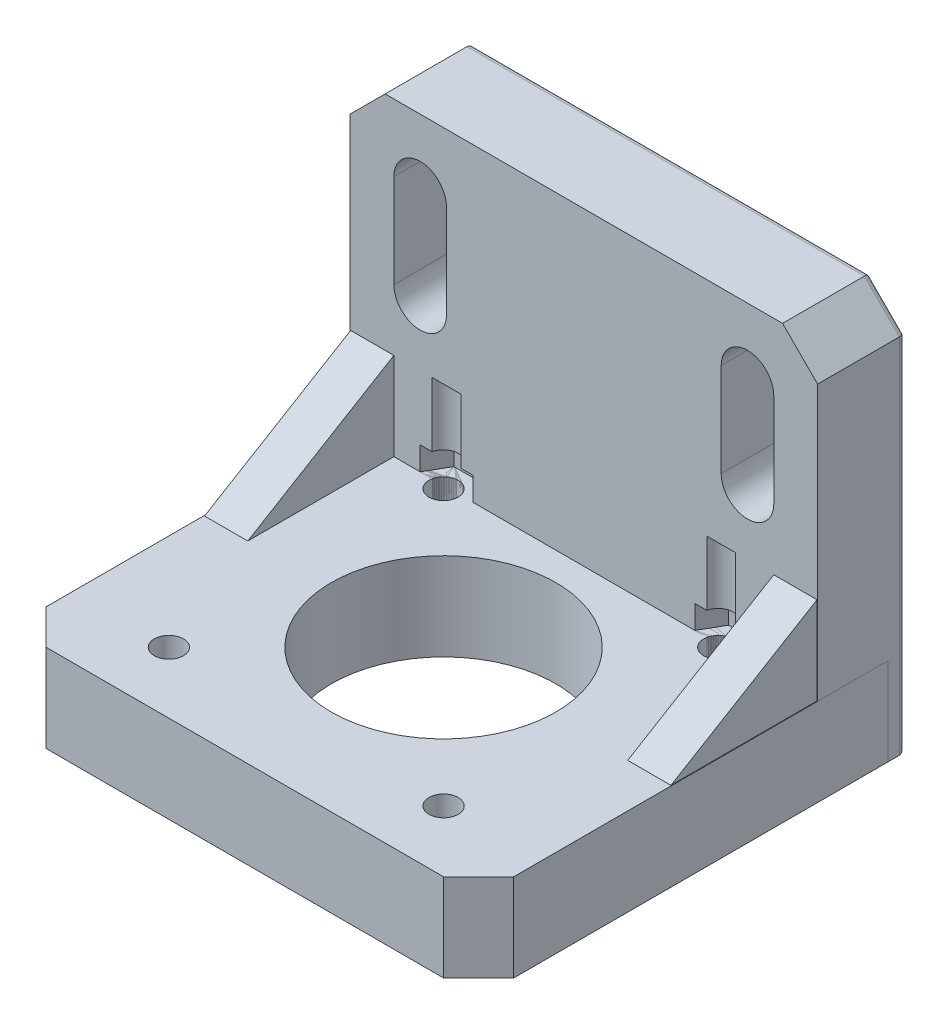
SolidWorks part; units mm, degrees
ref_plane "Front Plane" through (0, 0, 0) normal (0, 0, 1) x (1, 0, 0)
ref_plane "Top Plane" through (0, 0, 0) normal (0, 1, 0) x (1, 0, 0)
ref_plane "Right Plane" through (0, 0, 0) normal (1, 0, 0) x (0, 0, -1)
sketch "Sketch1" plane through (0, 0, 0) normal (0, 1, 0) x (1, 0, 0)
  line L1 (-32.5, -5) -> (47.5, -5)
  line L2 (-32.5, -5) -> (-32.5, 65)
  line L3 (-32.5, 65) -> (47.5, 65)
  line L4 (47.5, -5) -> (47.5, 65)
  dimension "D1" = 70
  dimension "D2" = 80
  dimension "D3" = 32.5
extrude "Boss-Extrude1" add sketch "Sketch1" along normal blind 15
sketch "Sketch2" plane through (0, 0, 0) normal (0, -1, 0) x (1, 0, 0)
  line L0 (47.5, 5) -> (47.5, -65) construction
  line L1 (-32.5, -65) -> (47.5, -65)
  line L2 (-32.5, -65) -> (-32.5, -68)
  line L3 (-32.5, -68) -> (47.5, -68)
  line L4 (47.5, -65) -> (47.5, -68)
  line L5 (-32.5, -53) -> (47.5, -53)
  line L6 (-32.5, -65) -> (-32.5, 5) construction
  line M2 (-32.5, 5) -> (-32.5, -65)
  line M3 (-32.5, -65) -> (47.5, -65)
  line M4 (47.5, -65) -> (47.5, 5)
  dimension "D1" = 3
  dimension "D2" = 12
extrude "Boss-Extrude2" add sketch "Sketch2" against normal blind 68 separate body contours L4 L2 L3 M3 | L5 M2 M3 M4 region at (7.5, 0, -59) region at (7.5, 0, -66.5)
sketch "Sketch4" plane through (0, 15, 0) normal (0, 1, 0) x (1, 0, 0)
  line L0 (-32.5, 65) -> (-32.5, -5) construction
  line L2 (-32.5, 68) -> (47.5, 68) construction
  circle A0 centre (7.5, 29) radius 19.2
  point P7 (7.5, 9.8)
  dimension "D1" = 38.4
  dimension "D2" = 39
  dimension "D3" = 40
  dimension "D4" = 39
extrude "Cut-Extrude1" cut sketch "Sketch4" against normal through all
sketch "Sketch5" plane through (0, 15, 0) normal (0, 1, 0) x (1, 0, 0)
  line L0 (33.396, 48.35) -> (28.604, 48.35)
  line L1 (-16, 52.5) -> (31, 52.5) construction
  line L2 (-16, 52.5) -> (-16, 5.5) construction
  line L3 (-16, 5.5) -> (31, 5.5) construction
  line L4 (31, 52.5) -> (31, 5.5) construction
  line L5 (-16, 52.5) -> (31, 5.5) construction
  line L6 (-16, 5.5) -> (31, 52.5) construction
  line L7 (28.604, 48.35) -> (26.208, 52.5)
  line L8 (26.208, 52.5) -> (28.604, 56.65)
  line L9 (28.604, 56.65) -> (33.396, 56.65)
  line L10 (33.396, 56.65) -> (35.792, 52.5)
  line L11 (35.792, 52.5) -> (33.396, 48.35)
  line L12 (-13.602, 56.65) -> (-11.206, 52.5)
  line L13 (-18.394, 48.35) -> (-20.79, 52.5)
  line L14 (-11.206, 52.5) -> (-13.602, 48.35)
  line L15 (-13.602, 48.35) -> (-18.394, 48.35)
  line L16 (-20.79, 52.5) -> (-18.394, 56.65)
  line L17 (-18.394, 56.65) -> (-13.602, 56.65)
  circle A0 centre (-16, 52.5) radius 2.5
  circle A1 centre (31, 52.5) radius 2.5
  circle A2 centre (31, 5.5) radius 2.5
  circle A3 centre (-16, 5.5) radius 2.5
  point P0 (7.5, 29)
  point P16 (7.5, 29)
  point P22 (31, 52.5)
  point P26 (0, 0)
  point P28 (-16.5743, 48.35)
  dimension "D2" = 5
  dimension "D1" = 47
  dimension "D4" = 8.3
  dimension "D5" = 8.3
  dimension "D6" = 4.15
  dimension "D7" = 4.792
  dimension "D8" = 9.584
  dimension "D9" = 8.3
  dimension "D10" = 8.3
  dimension "D11" = 4.15
  dimension "D12" = 4.79
  dimension "D3" = 4
extrude "Cut-Extrude2" cut sketch "Sketch5" against normal through all and the other way blind 15 contours A2 | A3 | A0 | A0 | A1 | A1 region at (-16, 15, -52.5) region at (31, 15, -52.5) region at (31, 15, -5.5) region at (-16, 15, -5.5)
sketch "Sketch6" plane through (0, 0, -53) normal (0, 0, 1) x (1, 0, 0)
  line L0 (7.5, 15) -> (7.5, 68) construction
  line L1 (-32.5, 15) -> (47.5, 15) construction
  line L3 (-20.5, 56.5) -> (-20.5, 40.5) construction
  line L4 (-16, 56.5) -> (-16, 40.5)
  line L5 (-25, 56.5) -> (-25, 40.5)
  line L7 (35.5, 56.5) -> (35.5, 40.5) construction
  line L8 (31, 56.5) -> (31, 40.5)
  line L9 (40, 56.5) -> (40, 40.5)
  line L10 (-32.5, 68) -> (47.5, 68) construction
  arc A0 (-16, 56.5) -> (-25, 56.5) centre (-20.5, 56.5) ccw
  arc A1 (-25, 40.5) -> (-16, 40.5) centre (-20.5, 40.5) ccw
  arc A2 (31, 56.5) -> (40, 56.5) centre (35.5, 56.5) cw
  arc A3 (40, 40.5) -> (31, 40.5) centre (35.5, 40.5) cw
  point P4 (0, 0)
  point P5 (0, 0)
  point P8 (-20.5, 48.5)
  point P13 (-20.5, 61)
  point P14 (-20.5, 36)
  point P17 (0, 0)
  point P18 (0, 0)
  point P21 (35.5, 48.5)
  point P26 (0, 0)
  dimension "D1" = 4.5
  dimension "D2" = 25
  dimension "D3" = 56
  dimension "D4" = 7
extrude "Cut-Extrude3" cut sketch "Sketch6" against normal up to surface (15 mm away) contours L5 A1 L4 A0 | A3 L9 A2 L8 region at (-20.5, 48.5, -53) region at (35.5, 48.5, -53) up to face at (7.5, 34, -68)
sketch "Sketch8" plane through (-32.5, 0, 0) normal (-1, 0, 0) x (0, 0, 1)
  line L0 (-28, 15) -> (-53, 30)
  line L1 (-65, 15) -> (5, 15) construction
  line L2 (-53, 68) -> (-53, 0) construction
  line L3 (-53, 30) -> (-53, 15)
  line L4 (-65, 15) -> (5, 15) construction
  line L5 (-53, 15) -> (-28, 15)
  point P4 (0, 0)
  point P6 (0, 0)
  point P9 (0, 0)
  point P11 (-53, 15)
  point P14 (-53, 15.2265)
  dimension "D1" = 25
  dimension "D2" = 15
extrude "Boss-Extrude3" add sketch "Sketch8" against normal up to surface (7.5 mm away) from offset 0.1 up to face at (-25, 48.5, -60.5) offset against normal yes
sketch "Sketch9" plane through (47.5, 0, 0) normal (1, 0, 0) x (0, 0, -1)
  line L3 (53, 15) -> (53, 30)
  line L4 (28, 15) -> (53, 15)
  line L5 (53, 15) -> (53, 30)
  line L7 (53, 30) -> (28, 15)
  line L8 (28, 15) -> (53, 15)
  line L11 (53, 30) -> (28, 15)
  dimension "D1" = 0
extrude "Boss-Extrude4" add sketch "Sketch9" against normal up to surface (7.5 mm away) from offset 0.1 up to face at (40, 48.5, -60.5) offset against normal yes
chamfer "Chamfer1" distance 6 angle 45 2 edges at (47.5, 7.5, 5) (-32.5, 7.5, 5)
extrude "Cut-Extrude7" cut sketch "Sketch5<5>" along normal blind 4 contours L17 L16 L13 L15 L14 L12 A0 | L11 L10 L9 L8 L7 L0 A1 | A1 | A0 region at (31, 15, -48.4768) region at (-12.5138, 15, -54.5116) region at (-16, 15, -52.5) region at (31, 15, -52.5)
sketch "Sketch5<5>" plane through (0, 15, 0) normal (0, 1, 0) x (1, 0, 0) same geometry as "Sketch5"
chamfer "Chamfer2" distance 6 angle 45 2 edges at (-32.5, 68, -60.5) (47.5, 68, -60.5)
fillet "Fillet3" radius 1 14 edges at (35.5, 61, -68) (40, 48.5, -68) (35.5, 36, -68) (31, 48.5, -68) (7.5, 0, -68) (47.5, 31, -68) (44.5, 65, -68) (7.5, 68, -68) (-29.5, 65, -68) (-32.5, 31, -68) (-25, 48.5, -68) (-20.5, 61, -68) (-16, 48.5, -68) (-20.5, 36, -68)
equation "\"D7@Sketch5\"=\"D8@Sketch5\"/2"
equation "\"D6@Sketch5\"=\"D5@Sketch5\"/2"
equation "\"D5@Sketch5\"=\"D4@Sketch5\""
